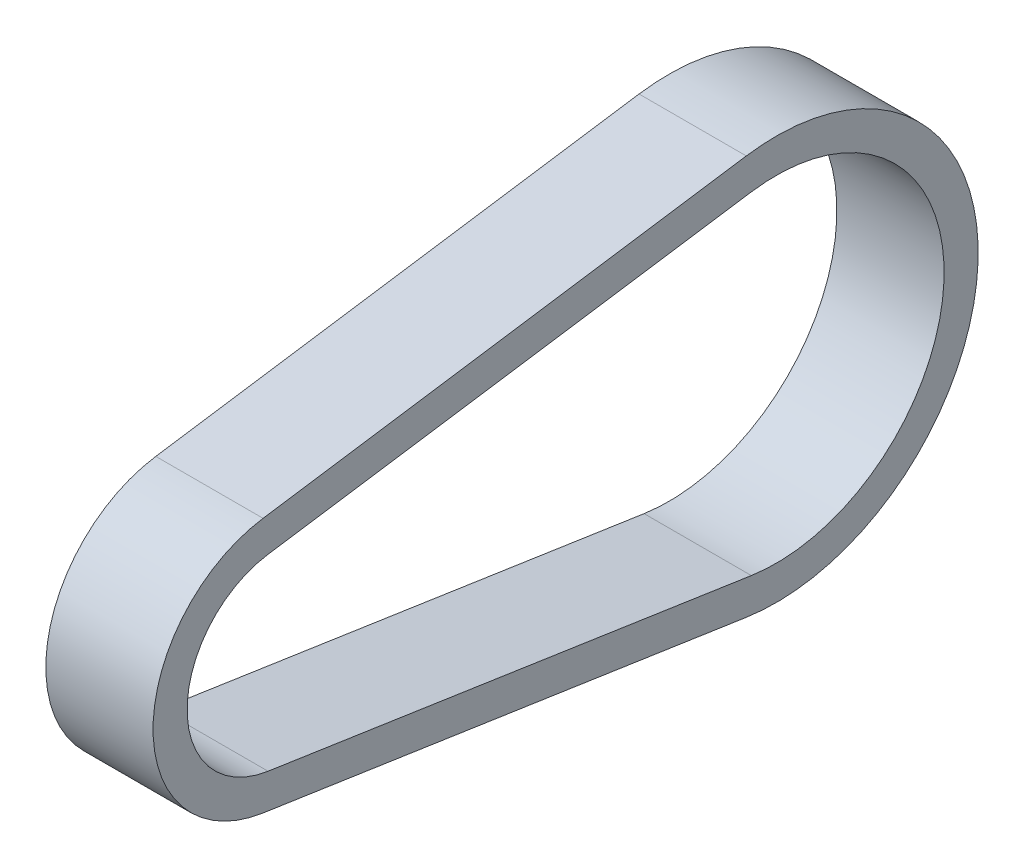
SolidWorks part; units mm, degrees
ref_plane "Front Plane" through (0, 0, 0) normal (0, 0, 1) x (1, 0, 0)
ref_plane "Top Plane" through (0, 0, 0) normal (0, 1, 0) x (1, 0, 0)
ref_plane "Right Plane" through (0, 0, 0) normal (1, 0, 0) x (0, 0, -1)
other "Bounding Box"
ref_plane "Default Plane" through (-8.9266, -12.7485, 0) normal (-0.1736, 0.9848, 0) x (0.9848, 0.1736, 0)
sketch "Sketch1" plane through (0, 0, 0) normal (1, 0, 0) x (0, 0, -1)
  line L0 (0, 0) -> (69.1007, 0) construction
  line L1 (-1.9625, 13.1384) -> (65.6302, 23.2347)
  line L2 (-1.9625, -13.1384) -> (65.6302, -23.2347)
  line L3 (-2.666, 17.8487) -> (64.9266, 27.9449)
  line L4 (-2.666, -17.8487) -> (64.9266, -27.9449)
  line L5 (-13.2842, 0) -> (-18.0467, 0) construction
  line L6 (92.5932, 0) -> (97.3557, 0) construction
  arc A0 (-1.9625, 13.1384) -> (-1.9625, -13.1384) centre (0, 0) ccw
  arc A1 (65.6302, -23.2347) -> (65.6302, 23.2347) centre (69.1007, 0) ccw
  arc A2 (-2.666, 17.8487) -> (-2.666, -17.8487) centre (0, 0) ccw
  arc A3 (64.9266, -27.9449) -> (64.9266, 27.9449) centre (69.1007, 0) ccw
  dimension "D2" = 4.7625
  dimension "D4" = 26.5684
  dimension "D5" = 46.9849
  dimension "D1" = 69.1007
extrude "Boss-Extrude1" add sketch "Sketch1" along normal mid plane 15
